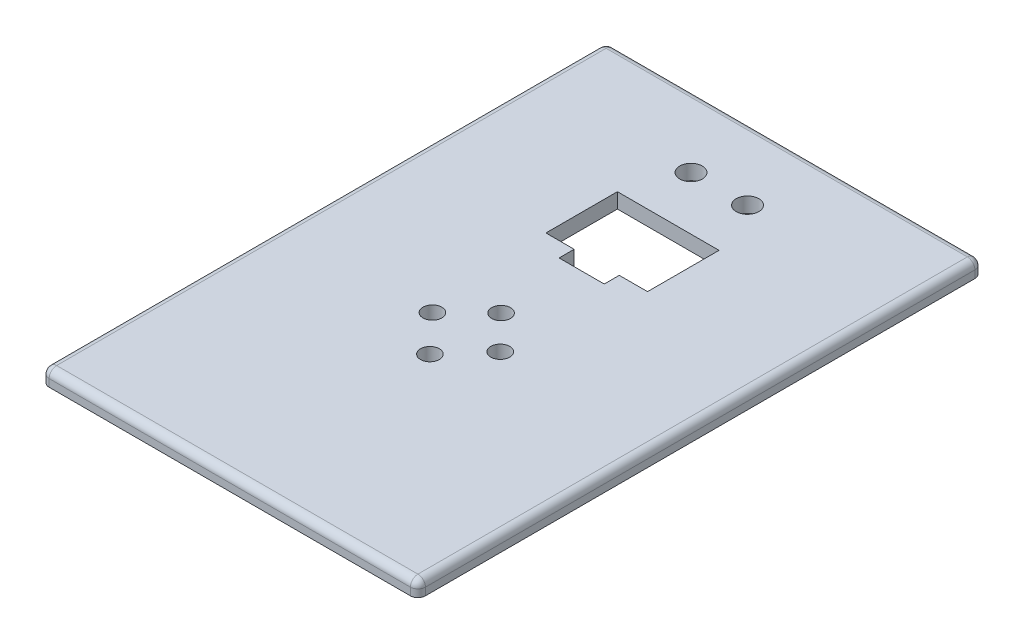
SolidWorks part; units mm, degrees
ref_plane "Front Plane" through (0, 0, 0) normal (0, 0, 1) x (1, 0, 0)
ref_plane "Top Plane" through (0, 0, 0) normal (0, 1, 0) x (1, 0, 0)
ref_plane "Right Plane" through (0, 0, 0) normal (1, 0, 0) x (0, 0, -1)
sketch "Sketch1" plane through (0, 0, 0) normal (0, 1, 0) x (1, 0, 0)
  line L1 (0, 0) -> (100, 0)
  line L2 (0, 0) -> (0, 150)
  line L3 (0, 150) -> (100, 150)
  line L4 (100, 0) -> (100, 150)
  dimension "D1" = 100
  dimension "D2" = 150
extrude "Boss-Extrude1" add sketch "Sketch1" along normal blind 4 contours L2 L1 L4 L3
sketch "Sketch2" plane through (0, 4, 0) normal (0, 1, 0) x (1, 0, 0)
  line L0 (0, 109.0711) -> (36.5, 109.0711) construction
  line L1 (36.5, 116.5084) -> (63.5, 116.5084)
  line L2 (36.5, 116.5084) -> (36.5, 97.5084)
  line L3 (36.5, 97.5084) -> (63.5, 97.5084)
  line L4 (63.5, 116.5084) -> (63.5, 97.5084)
  line L5 (0, 0) -> (0, 150) construction
  line L6 (36.5, 97.5084) -> (36.5, 78.9264) construction
  line L7 (44, 97.5084) -> (56, 97.5084)
  line L8 (44, 97.5084) -> (44, 93.5084)
  line L9 (44, 93.5084) -> (56, 93.5084)
  line L10 (56, 97.5084) -> (56, 93.5084)
  line L12 (44, 97.5084) -> (56, 97.5084)
  line L13 (44, 97.5084) -> (44, 93.5084)
  line L14 (44, 93.5084) -> (56, 93.5084)
  line L15 (56, 97.5084) -> (56, 93.5084)
  dimension "D1" = 27
  dimension "D2" = 19
  dimension "D3" = 36.5
  dimension "D4" = 12
  dimension "D5" = 4
  dimension "D6" = 7.5
extrude "Cut-Extrude1" cut sketch "Sketch2" against normal blind 4 contours L4 L1 L2 L3 region at (50, 4, -107.0084)
extrude "Cut-Extrude2" cut sketch "Sketch2<4>" against normal blind 4 contours L10 L3 L8 L9 region at (50, 4, -95.5084)
sketch "Sketch2<4>" plane through (0, 4, 0) normal (0, 1, 0) x (1, 0, 0) same geometry as "Sketch2"
sketch "Sketch3" plane through (0, 4, 0) normal (0, 1, 0) x (1, 0, 0)
  circle A0 centre (48.9759, 73.1295) radius 2.5
  circle A1 centre (48.9759, 54.2122) radius 2.5
  circle A2 centre (57.7747, 64.1108) radius 2.5
  circle A3 centre (39.7372, 64.1108) radius 2.5
  dimension "D1" = 5
  dimension "D2" = 5
  dimension "D3" = 5
  dimension "D4" = 5
extrude "Cut-Extrude3" cut sketch "Sketch3" against normal blind 4
sketch "Sketch4" plane through (0, 4, 0) normal (0, 1, 0) x (1, 0, 0)
  line L0 (50, 116.5084) -> (50, 146.4787) construction
  line L1 (36.5, 116.5084) -> (63.5, 116.5084) construction
  circle A0 centre (56.8816, 130.6962) radius 3
  circle A1 centre (41.869, 130.6962) radius 3
  dimension "D1" = 6
  dimension "D2" = 6
extrude "Cut-Extrude4" cut sketch "Sketch4" against normal blind 4
fillet "Fillet1" radius 2 8 edges at (0, 2, 0) (50, 4, 0) (100, 2, 0) (100, 4, -75) (100, 2, -150) (0, 2, -150) (0, 4, -75) (50, 4, -150)
